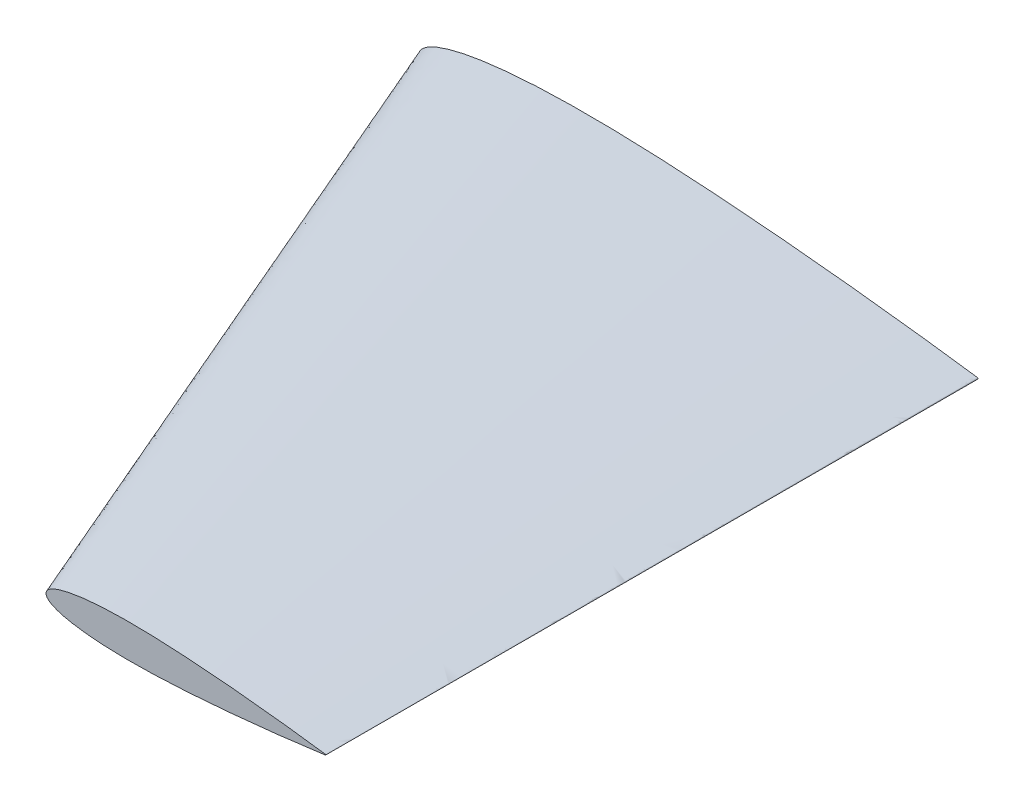
SolidWorks part; units mm, degrees
ref_plane "Front Plane" through (0, 0, 0) normal (1, 0, 0) x (0, 1, 0)
ref_plane "Top Plane" through (0, 0, 0) normal (0, 0, 1) x (0, 1, 0)
ref_plane "Right Plane" through (0, 0, 0) normal (0, 1, 0) x (-1, 0, 0)
curve "Curve1"
  spline degree 3 poles (120, 0.1512, 0) (119.9384, 0.1598, 0) (119.6921, 0.1944, 0) (119.1396, 0.2714, 0) (118.2224, 0.3987, 0) (116.9463, 0.5734, 0) (115.3191, 0.7934, 0) (113.3509, 1.0543, 0) (111.0537, 1.3526, 0) (108.4418, 1.6836, 0) (105.5312, 2.0429, 0) (102.3399, 2.4251, 0) (98.8876, 2.8257, 0) (95.1955, 3.2391, 0) (91.2864, 3.6604, 0) (87.1844, 4.0843, 0) (82.9149, 4.5053, 0) (78.504, 4.9175, 0) (73.9791, 5.3155, 0) (69.368, 5.6926, 0) (64.6991, 6.0428, 0) (60.0013, 6.3594, 0) (55.3033, 6.6359, 0) (50.6343, 6.8653, 0) (46.023, 7.0415, 0) (41.4977, 7.1587, 0) (37.0863, 7.2112, 0) (32.8161, 7.1949, 0) (28.7132, 7.1065, 0) (24.8031, 6.9438, 0) (21.1096, 6.7064, 0) (17.6556, 6.3951, 0) (14.4622, 6.0122, 0) (11.5488, 5.561, 0) (8.9331, 5.0463, 0) (6.6304, 4.4738, 0) (4.6538, 3.8491, 0) (3.0134, 3.1781, 0) (1.7143, 2.4652, 0) (0.7586, 1.7091, 0) (0.1465, 0.8915, 0) (-0.0683, 0, 0) (0.1465, -0.8915, 0) (0.7586, -1.7091, 0) (1.7143, -2.4652, 0) (3.0134, -3.1781, 0) (4.6538, -3.8491, 0) (6.6304, -4.4738, 0) (8.9331, -5.0463, 0) (11.5488, -5.561, 0) (14.4622, -6.0122, 0) (17.6556, -6.3951, 0) (21.1096, -6.7064, 0) (24.8031, -6.9438, 0) (28.7132, -7.1065, 0) (32.8161, -7.1949, 0) (37.0863, -7.2112, 0) (41.4977, -7.1587, 0) (46.023, -7.0415, 0) (50.6343, -6.8653, 0) (55.3033, -6.6359, 0) (60.0013, -6.3594, 0) (64.6991, -6.0428, 0) (69.368, -5.6926, 0) (73.9791, -5.3155, 0) (78.504, -4.9175, 0) (82.9149, -4.5053, 0) (87.1844, -4.0843, 0) (91.2864, -3.6604, 0) (95.1955, -3.2391, 0) (98.8876, -2.8257, 0) (102.3399, -2.4251, 0) (105.5312, -2.0429, 0) (108.4418, -1.6836, 0) (111.0537, -1.3526, 0) (113.3509, -1.0543, 0) (115.3191, -0.7934, 0) (116.9463, -0.5734, 0) (118.2224, -0.3987, 0) (119.1396, -0.2714, 0) (119.6921, -0.1944, 0) (119.9384, -0.1598, 0) (120, -0.1512, 0) knots 0 0 0 0 0.000763 0.003048 0.006841 0.012116 0.018841 0.026973 0.03646 0.047243 0.059254 0.072417 0.086651 0.101866 0.117969 0.134858 0.152428 0.170572 0.189175 0.208122 0.227297 0.24658 0.265853 0.284997 0.303895 0.322433 0.340499 0.357984 0.374788 0.390812 0.405965 0.420162 0.433328 0.445394 0.456301 0.466004 0.474472 0.481696 0.487704 0.492583 0.496544 0.5 0.503456 0.507417 0.512296 0.518304 0.525528 0.533996 0.543699 0.554606 0.566672 0.579838 0.594035 0.609188 0.625212 0.642016 0.659501 0.677567 0.696105 0.715003 0.734147 0.75342 0.772703 0.791878 0.810825 0.829428 0.847572 0.865142 0.882031 0.898134 0.913349 0.927583 0.940746 0.952757 0.96354 0.973027 0.981159 0.987884 0.993159 0.996952 0.999237 1 1 1 1
curve "Curve2"
  spline degree 3 poles (60, 0.0756, 0) (59.9883, 0.0772, 0) (59.9416, 0.0838, 0) (59.8367, 0.0985, 0) (59.6621, 0.1229, 0) (59.4182, 0.1568, 0) (59.1056, 0.2, 0) (58.725, 0.2522, 0) (58.2774, 0.3132, 0) (57.7637, 0.3825, 0) (57.1851, 0.4596, 0) (56.5431, 0.5442, 0) (55.839, 0.6357, 0) (55.0747, 0.7337, 0) (54.2517, 0.8375, 0) (53.3721, 0.9467, 0) (52.438, 1.0606, 0) (51.4514, 1.1787, 0) (50.4147, 1.3003, 0) (49.3304, 1.425, 0) (48.2009, 1.5521, 0) (47.0288, 1.6809, 0) (45.8171, 1.8109, 0) (44.5683, 1.9415, 0) (43.2856, 2.072, 0) (41.9718, 2.2018, 0) (40.6301, 2.3301, 0) (39.2635, 2.4565, 0) (37.8753, 2.58, 0) (36.4687, 2.7001, 0) (35.047, 2.816, 0) (33.6135, 2.927, 0) (32.1716, 3.0322, 0) (30.7246, 3.131, 0) (29.2759, 3.2225, 0) (27.8289, 3.3059, 0) (26.3869, 3.3806, 0) (24.9534, 3.4457, 0) (23.5317, 3.5004, 0) (22.1251, 3.5442, 0) (20.7368, 3.5763, 0) (19.3702, 3.5962, 0) (18.0284, 3.6032, 0) (16.7145, 3.597, 0) (15.4317, 3.5772, 0) (14.1829, 3.5434, 0) (12.971, 3.4956, 0) (11.7988, 3.4335, 0) (10.6691, 3.3571, 0) (9.5846, 3.2667, 0) (8.5477, 3.1624, 0) (7.5609, 3.0445, 0) (6.6264, 2.9134, 0) (5.7465, 2.7696, 0) (4.9231, 2.6137, 0) (4.1582, 2.4461, 0) (3.4535, 2.2677, 0) (2.8107, 2.0791, 0) (2.231, 1.8809, 0) (1.7158, 1.6738, 0) (1.2661, 1.4585, 0) (0.8827, 1.2355, 0) (0.5661, 1.0049, 0) (0.3168, 0.7666, 0) (0.1356, 0.5197, 0) (0.0247, 0.2632, 0) (-0.0121, 0, 0) (0.0247, -0.2632, 0) (0.1356, -0.5197, 0) (0.3168, -0.7666, 0) (0.5661, -1.0049, 0) (0.8827, -1.2355, 0) (1.2661, -1.4585, 0) (1.7158, -1.6738, 0) (2.231, -1.8809, 0) (2.8107, -2.0791, 0) (3.4535, -2.2677, 0) (4.1582, -2.4461, 0) (4.9231, -2.6137, 0) (5.7465, -2.7696, 0) (6.6264, -2.9134, 0) (7.5609, -3.0445, 0) (8.5477, -3.1624, 0) (9.5846, -3.2667, 0) (10.6691, -3.3571, 0) (11.7988, -3.4335, 0) (12.971, -3.4956, 0) (14.1829, -3.5434, 0) (15.4317, -3.5772, 0) (16.7145, -3.597, 0) (18.0284, -3.6032, 0) (19.3702, -3.5962, 0) (20.7368, -3.5763, 0) (22.1251, -3.5442, 0) (23.5317, -3.5004, 0) (24.9534, -3.4457, 0) (26.3869, -3.3806, 0) (27.8289, -3.3059, 0) (29.2759, -3.2225, 0) (30.7246, -3.131, 0) (32.1716, -3.0322, 0) (33.6135, -2.927, 0) (35.047, -2.816, 0) (36.4687, -2.7001, 0) (37.8753, -2.58, 0) (39.2635, -2.4565, 0) (40.6301, -2.3301, 0) (41.9718, -2.2018, 0) (43.2856, -2.072, 0) (44.5683, -1.9415, 0) (45.8171, -1.8109, 0) (47.0288, -1.6809, 0) (48.2009, -1.5521, 0) (49.3304, -1.425, 0) (50.4147, -1.3003, 0) (51.4514, -1.1787, 0) (52.438, -1.0606, 0) (53.3721, -0.9467, 0) (54.2517, -0.8375, 0) (55.0747, -0.7337, 0) (55.839, -0.6357, 0) (56.5431, -0.5442, 0) (57.1851, -0.4596, 0) (57.7637, -0.3825, 0) (58.2774, -0.3132, 0) (58.725, -0.2522, 0) (59.1056, -0.2, 0) (59.4182, -0.1568, 0) (59.6621, -0.1229, 0) (59.8367, -0.0985, 0) (59.9416, -0.0838, 0) (59.9883, -0.0772, 0) (60, -0.0756, 0) knots 0 0 0 0 0.000289 0.001156 0.002598 0.004612 0.007194 0.010336 0.014031 0.018271 0.023046 0.028343 0.03415 0.040454 0.047239 0.054489 0.062186 0.070314 0.078852 0.08778 0.097077 0.106722 0.116691 0.126961 0.137507 0.148306 0.159331 0.170557 0.181957 0.193504 0.205172 0.216932 0.228758 0.240621 0.252495 0.26435 0.276161 0.287898 0.299536 0.311047 0.322405 0.333584 0.344559 0.355306 0.3658 0.376018 0.385938 0.395538 0.404798 0.413699 0.422222 0.430349 0.438066 0.445357 0.452209 0.458611 0.464554 0.47003 0.475035 0.479569 0.483637 0.48725 0.490431 0.493219 0.495674 0.497891 0.5 0.502109 0.504326 0.506781 0.509569 0.51275 0.516363 0.520431 0.524965 0.52997 0.535446 0.541389 0.547791 0.554643 0.561934 0.569651 0.577778 0.586301 0.595202 0.604462 0.614062 0.623982 0.6342 0.644694 0.655441 0.666416 0.677595 0.688953 0.700464 0.712102 0.723839 0.73565 0.747505 0.759379 0.771242 0.783068 0.794828 0.806496 0.818043 0.829443 0.840669 0.851694 0.862493 0.873039 0.883309 0.893278 0.902923 0.91222 0.921148 0.929686 0.937814 0.945511 0.952761 0.959546 0.96585 0.971657 0.976954 0.981729 0.985969 0.989664 0.992806 0.995388 0.997402 0.998844 0.999711 1 1 1 1
sketch "Sketch3" plane through (0, 0, 0) normal (0, 0, 1) x (0, 1, 0)
  arc A0 (-0.1512, -120) -> (0.1512, -120) centre (0, -119.9788) ccw
  spline S0 degree 3 poles (1963.2865, -496.8861) (-12.8593, -186.2558) (-4.4646, -153.1098) (0.2714, -119.1396) (0.3987, -118.2224) (0.5734, -116.9463) (0.7934, -115.3191) (1.0543, -113.3509) (1.3526, -111.0537) (1.6836, -108.4418) (2.0429, -105.5312) (2.4251, -102.3399) (2.8257, -98.8876) (3.2391, -95.1955) (3.6604, -91.2864) (4.0843, -87.1844) (4.5053, -82.9149) (4.9175, -78.504) (5.3155, -73.9791) (5.6926, -69.368) (6.0428, -64.6991) (6.3594, -60.0013) (6.6359, -55.3033) (6.8653, -50.6343) (7.0415, -46.023) (7.1587, -41.4977) (7.2112, -37.0863) (7.1949, -32.8161) (7.1065, -28.7132) (6.9438, -24.8031) (6.7064, -21.1096) (6.3951, -17.6556) (6.0122, -14.4622) (5.561, -11.5488) (5.0463, -8.9331) (4.4738, -6.6304) (3.8491, -4.6538) (3.1781, -3.0134) (2.4652, -1.7143) (1.7091, -0.7586) (0.8915, -0.1465) (0, 0.0683) (-0.8915, -0.1465) (-1.7091, -0.7586) (-2.4652, -1.7143) (-3.1781, -3.0134) (-3.8491, -4.6538) (-4.4738, -6.6304) (-5.0463, -8.9331) (-5.561, -11.5488) (-6.0122, -14.4622) (-6.3951, -17.6556) (-6.7064, -21.1096) (-6.9438, -24.8031) (-7.1065, -28.7132) (-7.1949, -32.8161) (-7.2112, -37.0863) (-7.1587, -41.4977) (-7.0415, -46.023) (-6.8653, -50.6343) (-6.6359, -55.3033) (-6.3594, -60.0013) (-6.0428, -64.6991) (-5.6926, -69.368) (-5.3155, -73.9791) (-4.9175, -78.504) (-4.5053, -82.9149) (-4.0843, -87.1844) (-3.6604, -91.2864) (-3.2391, -95.1955) (-2.8257, -98.8876) (-2.4251, -102.3399) (-2.0429, -105.5312) (-1.6836, -108.4418) (-1.3526, -111.0537) (-1.0543, -113.3509) (-0.7934, -115.3191) (-0.5734, -116.9463) (-0.3987, -118.2224) (-0.2714, -119.1396) (4.4646, -153.1096) (12.8592, -186.2554) (-1963.2505, -496.8804) knots -0.413697 -0.413697 -0.413697 -0.413697 0.000763 0.003048 0.006841 0.012116 0.018841 0.026973 0.03646 0.047243 0.059254 0.072417 0.086651 0.101866 0.117969 0.134858 0.152428 0.170572 0.189175 0.208122 0.227297 0.24658 0.265853 0.284997 0.303895 0.322433 0.340499 0.357984 0.374788 0.390812 0.405965 0.420162 0.433328 0.445394 0.456301 0.466004 0.474472 0.481696 0.487704 0.492583 0.496544 0.5 0.503456 0.507417 0.512296 0.518304 0.525528 0.533996 0.543699 0.554606 0.566672 0.579838 0.594035 0.609188 0.625212 0.642016 0.659501 0.677567 0.696105 0.715003 0.734147 0.75342 0.772703 0.791878 0.810825 0.829428 0.847572 0.865142 0.882031 0.898134 0.913349 0.927583 0.940746 0.952757 0.96354 0.973027 0.981159 0.987884 0.993159 0.996952 0.999237 1.413694 1.413694 1.413694 1.413694 only from (0.1512, -120) to (-0.1512, -120) construction
  spline S1 degree 3 poles (0.1512, -120) (0.1598, -119.9384) (0.1944, -119.6921) (0.2714, -119.1396) (0.3987, -118.2224) (0.5734, -116.9463) (0.7934, -115.3191) (1.0543, -113.3509) (1.3526, -111.0537) (1.6836, -108.4418) (2.0429, -105.5312) (2.4251, -102.3399) (2.8257, -98.8876) (3.2391, -95.1955) (3.6604, -91.2864) (4.0843, -87.1844) (4.5053, -82.9149) (4.9175, -78.504) (5.3155, -73.9791) (5.6926, -69.368) (6.0428, -64.6991) (6.3594, -60.0013) (6.6359, -55.3033) (6.8653, -50.6343) (7.0415, -46.023) (7.1587, -41.4977) (7.2112, -37.0863) (7.1949, -32.8161) (7.1065, -28.7132) (6.9438, -24.8031) (6.7064, -21.1096) (6.3951, -17.6556) (6.0122, -14.4622) (5.561, -11.5488) (5.0463, -8.9331) (4.4738, -6.6304) (3.8491, -4.6538) (3.1781, -3.0134) (2.4652, -1.7143) (1.7091, -0.7586) (0.8915, -0.1465) (0, 0.0683) (-0.8915, -0.1465) (-1.7091, -0.7586) (-2.4652, -1.7143) (-3.1781, -3.0134) (-3.8491, -4.6538) (-4.4738, -6.6304) (-5.0463, -8.9331) (-5.561, -11.5488) (-6.0122, -14.4622) (-6.3951, -17.6556) (-6.7064, -21.1096) (-6.9438, -24.8031) (-7.1065, -28.7132) (-7.1949, -32.8161) (-7.2112, -37.0863) (-7.1587, -41.4977) (-7.0415, -46.023) (-6.8653, -50.6343) (-6.6359, -55.3033) (-6.3594, -60.0013) (-6.0428, -64.6991) (-5.6926, -69.368) (-5.3155, -73.9791) (-4.9175, -78.504) (-4.5053, -82.9149) (-4.0843, -87.1844) (-3.6604, -91.2864) (-3.2391, -95.1955) (-2.8257, -98.8876) (-2.4251, -102.3399) (-2.0429, -105.5312) (-1.6836, -108.4418) (-1.3526, -111.0537) (-1.0543, -113.3509) (-0.7934, -115.3191) (-0.5734, -116.9463) (-0.3987, -118.2224) (-0.2714, -119.1396) (-0.1944, -119.6921) (-0.1598, -119.9384) (-0.1512, -120) knots 0 0 0 0 0.000763 0.003048 0.006841 0.012116 0.018841 0.026973 0.03646 0.047243 0.059254 0.072417 0.086651 0.101866 0.117969 0.134858 0.152428 0.170572 0.189175 0.208122 0.227297 0.24658 0.265853 0.284997 0.303895 0.322433 0.340499 0.357984 0.374788 0.390812 0.405965 0.420162 0.433328 0.445394 0.456301 0.466004 0.474472 0.481696 0.487704 0.492583 0.496544 0.5 0.503456 0.507417 0.512296 0.518304 0.525528 0.533996 0.543699 0.554606 0.566672 0.579838 0.594035 0.609188 0.625212 0.642016 0.659501 0.677567 0.696105 0.715003 0.734147 0.75342 0.772703 0.791878 0.810825 0.829428 0.847572 0.865142 0.882031 0.898134 0.913349 0.927583 0.940746 0.952757 0.96354 0.973027 0.981159 0.987884 0.993159 0.996952 0.999237 1 1 1 1
ref_plane "Plane2" through (0, 0, 140) normal (0, 0, 1) x (0, 1, 0)
sketch "Sketch4" plane through (0, 0, 140) normal (0, 0, 1) x (0, 1, 0)
  arc A4 (-0.0756, -119.9894) -> (0.0756, -119.9894) centre (0, -119.9788) ccw
  spline S2 degree 3 poles (0.0756, -119.9894) (0.0772, -119.9778) (0.0837, -119.9311) (0.0984, -119.8261) (0.1228, -119.6515) (0.1951, -119.1314) (0.282, -118.4981) (0.3824, -117.7531) (0.4596, -117.1746) (0.5442, -116.5325) (0.6357, -115.8285) (0.7336, -115.0641) (0.8375, -114.2412) (1.0752, -112.3257) (1.3139, -110.3072) (1.552, -108.1903) (1.7266, -106.602) (1.9003, -104.9623) (2.1175, -102.8277) (2.3346, -100.5953) (2.541, -98.3209) (2.7409, -95.9803) (2.8923, -94.0775) (3.0322, -92.161) (3.1309, -90.714) (3.2224, -89.2653) (3.3059, -87.8183) (3.3805, -86.3764) (3.4456, -84.9429) (3.5004, -83.5211) (3.5442, -82.1145) (3.5763, -80.7263) (3.5961, -79.3596) (3.6032, -78.0178) (3.597, -76.704) (3.5772, -75.4211) (3.5434, -74.1723) (3.4955, -72.9604) (3.4334, -71.7882) (3.3571, -70.6586) (3.2667, -69.574) (3.1624, -68.5371) (3.0445, -67.5503) (2.9134, -66.6159) (2.7696, -65.7359) (2.6136, -64.9126) (2.4461, -64.1477) (2.2677, -63.443) (2.079, -62.8001) (1.8808, -62.2204) (1.6738, -61.7052) (1.4585, -61.2555) (1.2354, -60.8721) (1.0048, -60.5555) (0.7665, -60.3062) (0.5197, -60.125) (0.2632, -60.0142) (0, -59.9774) (-0.2633, -60.0142) (-0.5198, -60.125) (-0.7666, -60.3062) (-1.0049, -60.5555) (-1.2355, -60.8721) (-1.4586, -61.2555) (-1.6739, -61.7052) (-1.8809, -62.2204) (-2.0791, -62.8001) (-2.2678, -63.443) (-2.4462, -64.1477) (-2.6137, -64.9126) (-2.7697, -65.7359) (-2.9135, -66.6159) (-3.0446, -67.5503) (-3.1625, -68.5371) (-3.2668, -69.574) (-3.3572, -70.6586) (-3.4335, -71.7882) (-3.4956, -72.9604) (-3.5435, -74.1723) (-3.5773, -75.4211) (-3.5971, -76.704) (-3.6033, -78.0178) (-3.5962, -79.3596) (-3.5764, -80.7263) (-3.5442, -82.1145) (-3.5005, -83.5211) (-3.4457, -84.9429) (-3.3806, -86.3764) (-3.306, -87.8183) (-3.2225, -89.2653) (-3.131, -90.714) (-3.0323, -92.161) (-2.8924, -94.0775) (-2.741, -95.9803) (-2.5411, -98.3209) (-2.3346, -100.5953) (-2.077, -103.2446) (-1.8569, -105.3788) (-1.681, -107.0183) (-1.5521, -108.1903) (-1.314, -110.3072) (-1.0752, -112.3257) (-0.8375, -114.2412) (-0.7337, -115.0641) (-0.6358, -115.8285) (-0.5442, -116.5325) (-0.4597, -117.1746) (-0.3456, -118.0295) (-0.2444, -118.7744) (-0.1568, -119.4076) (-0.1229, -119.6515) (-0.0985, -119.8261) (-0.0838, -119.9311) (-0.0773, -119.9778) (-0.0756, -119.9894) knots 0 0 0 0 0.000289 0.001156 0.002598 0.004612 0.014031 0.018271 0.023046 0.028343 0.03415 0.040454 0.047239 0.054489 0.08778 0.097077 0.106722 0.126961 0.137507 0.159331 0.181957 0.193504 0.216932 0.228758 0.240621 0.252495 0.26435 0.276161 0.287898 0.299536 0.311047 0.322405 0.333584 0.344559 0.355306 0.3658 0.376018 0.385938 0.395538 0.404798 0.413699 0.422222 0.430349 0.438066 0.445357 0.452209 0.458611 0.464554 0.47003 0.475035 0.479569 0.483637 0.48725 0.490431 0.493219 0.495674 0.497891 0.5 0.502109 0.504326 0.506781 0.509569 0.51275 0.516363 0.520431 0.524965 0.52997 0.535446 0.541389 0.547791 0.554643 0.561934 0.569651 0.577778 0.586301 0.595202 0.604462 0.614062 0.623982 0.6342 0.644694 0.655441 0.666416 0.677595 0.688953 0.700464 0.712102 0.723839 0.73565 0.747505 0.759379 0.771242 0.783068 0.806496 0.818043 0.840669 0.862493 0.883309 0.893278 0.902923 0.91222 0.945511 0.952761 0.959546 0.96585 0.971657 0.976954 0.981729 0.992806 0.995388 0.997402 0.998844 0.999711 1 1 1 1
loft "Loft1" add profiles "Sketch3", "Sketch4"
sketch "Sketch5" plane through (0, 0, 0) normal (0, 0, -1) x (1, 0, 0)
  circle A0 centre (59.9788, 0) radius 3.175
  arc A2 (120, -0.1512) -> (120, 0.1512) centre (119.9788, 0) ccw
  arc A3 (120, -0.1512) -> (120, 0.1512) centre (119.9788, 0) ccw
  spline S2 degree 3 poles (2119.9475, -2119.2172) (88.467, 73.5642) (-7.4592, 9.2673) (0.7585, -1.7091) (1.7141, -2.4652) (3.0132, -3.1781) (4.6536, -3.8491) (6.6302, -4.4738) (8.9329, -5.0463) (11.5486, -5.5611) (14.4621, -6.0122) (17.6555, -6.3951) (21.1095, -6.7064) (24.803, -6.9438) (28.7131, -7.1065) (32.816, -7.1949) (37.0862, -7.2112) (41.4976, -7.1587) (46.0229, -7.0415) (50.6342, -6.8653) (55.3033, -6.6359) (60.0012, -6.3594) (64.6991, -6.0428) (69.368, -5.6926) (73.9791, -5.3155) (78.504, -4.9175) (82.9148, -4.5053) (87.1844, -4.0843) (91.2864, -3.6604) (95.1955, -3.2392) (98.8876, -2.8257) (102.3399, -2.4251) (105.5312, -2.0429) (108.4418, -1.6836) (111.0537, -1.3526) (113.3509, -1.0543) (115.3191, -0.7934) (116.9463, -0.5734) (118.2224, -0.3987) (119.1396, -0.2714) (157.9529, 5.1398) (195.7823, 15.3513) (649.9649, -2951.4825) knots -0.152784 -0.152784 -0.152784 -0.152784 0.003456 0.007417 0.012296 0.018304 0.025528 0.033996 0.043699 0.054606 0.066672 0.079838 0.094035 0.109188 0.125212 0.142016 0.159501 0.177567 0.196105 0.215003 0.234147 0.25342 0.272703 0.291878 0.310825 0.329428 0.347572 0.365142 0.382031 0.398134 0.413349 0.427583 0.440746 0.452757 0.46354 0.473027 0.481159 0.487884 0.493159 0.496952 0.499237 0.973652 0.973652 0.973652 0.973652 only from (-0.0002, 0) to (120, -0.1512)
  spline S3 degree 3 poles (461.0436, -2895.7858) (729.0476, -278.0991) (431.132, -38.6969) (104.835, 2.1364) (97.239, 3.0204) (90.903, 3.7041) (84.5629, 4.3482) (79.4875, 4.8306) (74.409, 5.2774) (70.5984, 5.5933) (66.7862, 5.8885) (62.9723, 6.1614) (59.1567, 6.4099) (55.3395, 6.6314) (51.5206, 6.8228) (47.7002, 6.9808) (43.8784, 7.1016) (40.0556, 7.1802) (36.232, 7.211) (33.0456, 7.1913) (30.4969, 7.1443) (28.5858, 7.092) (26.6753, 7.0215) (24.7656, 6.931) (22.857, 6.819) (20.95, 6.683) (19.045, 6.5208) (17.1428, 6.3292) (15.2441, 6.1046) (13.3503, 5.8421) (11.7776, 5.5867) (10.524, 5.3562) (9.5866, 5.1687) (8.6527, 4.965) (7.7227, 4.7434) (6.7981, 4.5007) (5.8799, 4.2344) (4.9705, 3.9393) (4.0729, 3.6103) (3.1916, 3.2386) (2.3358, 2.8121) (1.5185, 2.3128) (0.7755, 1.7074) (-7.7702, -9.0011) (82.4901, -76.2927) (2232.3644, 1999.1772) knots -3.429668 -3.429668 -3.429668 -3.429668 0.532086 0.56328 0.594474 0.625669 0.641266 0.67246 0.688057 0.703654 0.719251 0.734849 0.750446 0.766043 0.78164 0.797237 0.812834 0.828431 0.844029 0.859626 0.867424 0.875223 0.883021 0.89082 0.898619 0.906417 0.914216 0.922014 0.929813 0.937611 0.94541 0.949309 0.953209 0.957108 0.961007 0.964906 0.968806 0.972705 0.976604 0.980504 0.984403 0.988302 0.992201 0.996101 1.154232 1.154232 1.154232 1.154232 only from (120, 0.1512) to (-0.0002, 0)
  spline S4 degree 3 poles (-0.0002, 0) (-0.0002, -0.2834) (0.1464, -0.8915) (0.7585, -1.7091) (1.7141, -2.4652) (3.0132, -3.1781) (4.6536, -3.8491) (6.6302, -4.4738) (8.9329, -5.0463) (11.5486, -5.5611) (14.4621, -6.0122) (17.6555, -6.3951) (21.1095, -6.7064) (24.803, -6.9438) (28.7131, -7.1065) (32.816, -7.1949) (37.0862, -7.2112) (41.4976, -7.1587) (46.0229, -7.0415) (50.6342, -6.8653) (55.3033, -6.6359) (60.0012, -6.3594) (64.6991, -6.0428) (69.368, -5.6926) (73.9791, -5.3155) (78.504, -4.9175) (82.9148, -4.5053) (87.1844, -4.0843) (91.2864, -3.6604) (95.1955, -3.2392) (98.8876, -2.8257) (102.3399, -2.4251) (105.5312, -2.0429) (108.4418, -1.6836) (111.0537, -1.3526) (113.3509, -1.0543) (115.3191, -0.7934) (116.9463, -0.5734) (118.2224, -0.3987) (119.1396, -0.2714) (119.6921, -0.1944) (119.9384, -0.1598) (120, -0.1512) knots 0 0 0 0 0.003456 0.007417 0.012296 0.018304 0.025528 0.033996 0.043699 0.054606 0.066672 0.079838 0.094035 0.109188 0.125212 0.142016 0.159501 0.177567 0.196105 0.215003 0.234147 0.25342 0.272703 0.291878 0.310825 0.329428 0.347572 0.365142 0.382031 0.398134 0.413349 0.427583 0.440746 0.452757 0.46354 0.473027 0.481159 0.487884 0.493159 0.496952 0.499237 0.5 0.5 0.5 0.5
  spline S5 degree 3 poles (120, 0.1512) (117.4756, 0.5052) (112.4232, 1.1868) (104.835, 2.1364) (97.239, 3.0204) (90.903, 3.7041) (84.5629, 4.3482) (79.4875, 4.8306) (74.409, 5.2774) (70.5984, 5.5933) (66.7862, 5.8885) (62.9723, 6.1614) (59.1567, 6.4099) (55.3395, 6.6314) (51.5206, 6.8228) (47.7002, 6.9808) (43.8784, 7.1016) (40.0556, 7.1802) (36.232, 7.211) (33.0456, 7.1913) (30.4969, 7.1443) (28.5858, 7.092) (26.6753, 7.0215) (24.7656, 6.931) (22.857, 6.819) (20.95, 6.683) (19.045, 6.5208) (17.1428, 6.3292) (15.2441, 6.1046) (13.3503, 5.8421) (11.7776, 5.5867) (10.524, 5.3562) (9.5866, 5.1687) (8.6527, 4.965) (7.7227, 4.7434) (6.7981, 4.5007) (5.8799, 4.2344) (4.9705, 3.9393) (4.0729, 3.6103) (3.1916, 3.2386) (2.3358, 2.8121) (1.5185, 2.3128) (0.7755, 1.7074) (0.1731, 0.9524) (-0.0002, 0.3175) (-0.0002, 0) knots 0.500891 0.500891 0.500891 0.500891 0.532086 0.56328 0.594474 0.625669 0.641266 0.67246 0.688057 0.703654 0.719251 0.734849 0.750446 0.766043 0.78164 0.797237 0.812834 0.828431 0.844029 0.859626 0.867424 0.875223 0.883021 0.89082 0.898619 0.906417 0.914216 0.922014 0.929813 0.937611 0.94541 0.949309 0.953209 0.957108 0.961007 0.964906 0.968806 0.972705 0.976604 0.980504 0.984403 0.988302 0.992201 0.996101 1 1 1 1
  dimension "D1" = 6.35
  dimension "D3" = 60
  dimension "D2" = 0
extrude "Cut-Extrude1" cut sketch "Sketch5" against normal blind 40 contours A0
